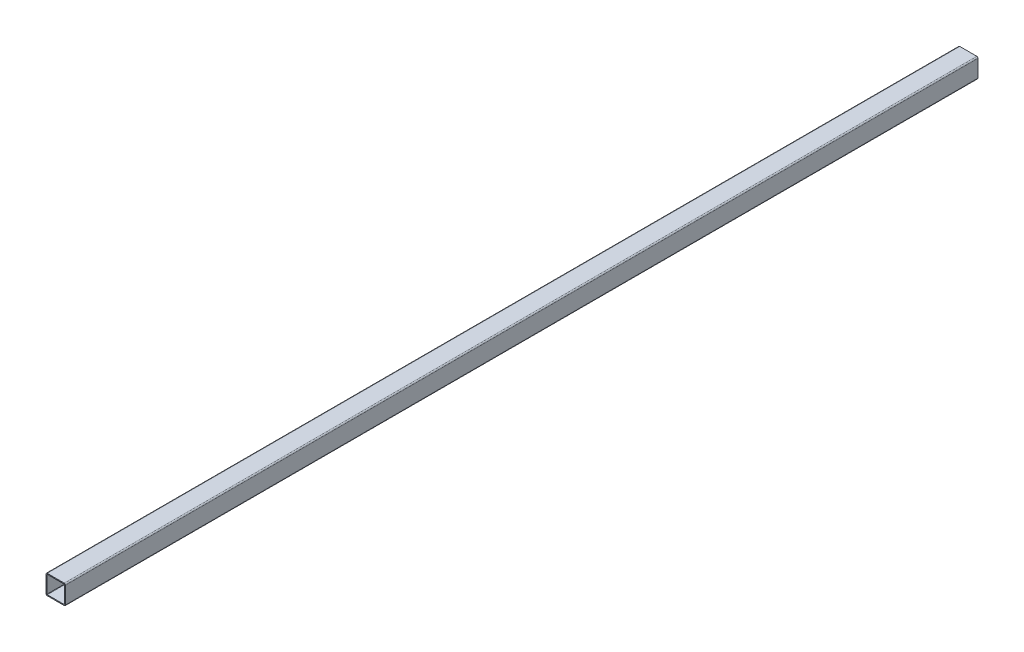
SolidWorks part; units mm, degrees
material "AISI 1010 Steel, hot rolled bar"
ref_plane "Front Plane" through (0, 0, 0) normal (0, 0, 1) x (1, 0, 0)
ref_plane "Top Plane" through (0, 0, 0) normal (0, 1, 0) x (1, 0, 0)
ref_plane "Right Plane" through (0, 0, 0) normal (1, 0, 0) x (0, 0, -1)
sketch "Sketch1" plane through (0, 0, 0) normal (0, 0, 1) x (1, 0, 0)
  line L0 (-14, 14.48) -> (14, 14.48)
  line L1 (-14, -16) -> (14, -16)
  line L2 (-16, -14) -> (-16, 14)
  line L3 (-14, 16) -> (14, 16)
  line L4 (16, -14) -> (16, 14)
  line L5 (-16, -16) -> (16, 16) construction
  line L6 (-16, 16) -> (16, -16) construction
  line L7 (14.48, -14) -> (14.48, 14)
  line L8 (-14, -14.48) -> (14, -14.48)
  line L9 (-14.48, -14) -> (-14.48, 14)
  arc A0 (14, -16) -> (16, -14) centre (14, -14) ccw
  arc A1 (-16, 14) -> (-14, 16) centre (-14, 14) cw
  arc A2 (-16, -14) -> (-14, -16) centre (-14, -14) ccw
  arc A3 (16, 14) -> (14, 16) centre (14, 14) ccw
  arc A4 (14.48, 14) -> (14, 14.48) centre (14, 14) ccw
  arc A5 (14, -14.48) -> (14.48, -14) centre (14, -14) ccw
  arc A6 (-14.48, -14) -> (-14, -14.48) centre (-14, -14) ccw
  arc A7 (-14.48, 14) -> (-14, 14.48) centre (-14, 14) cw
  point P0 (0, 0)
  dimension "D3" = 2
  dimension "D1" = 32
  dimension "D2" = 32
  dimension "D4" = 1.52
extrude "Boss-Extrude1" add sketch "Sketch1" along normal blind 750 and the other way blind 750
